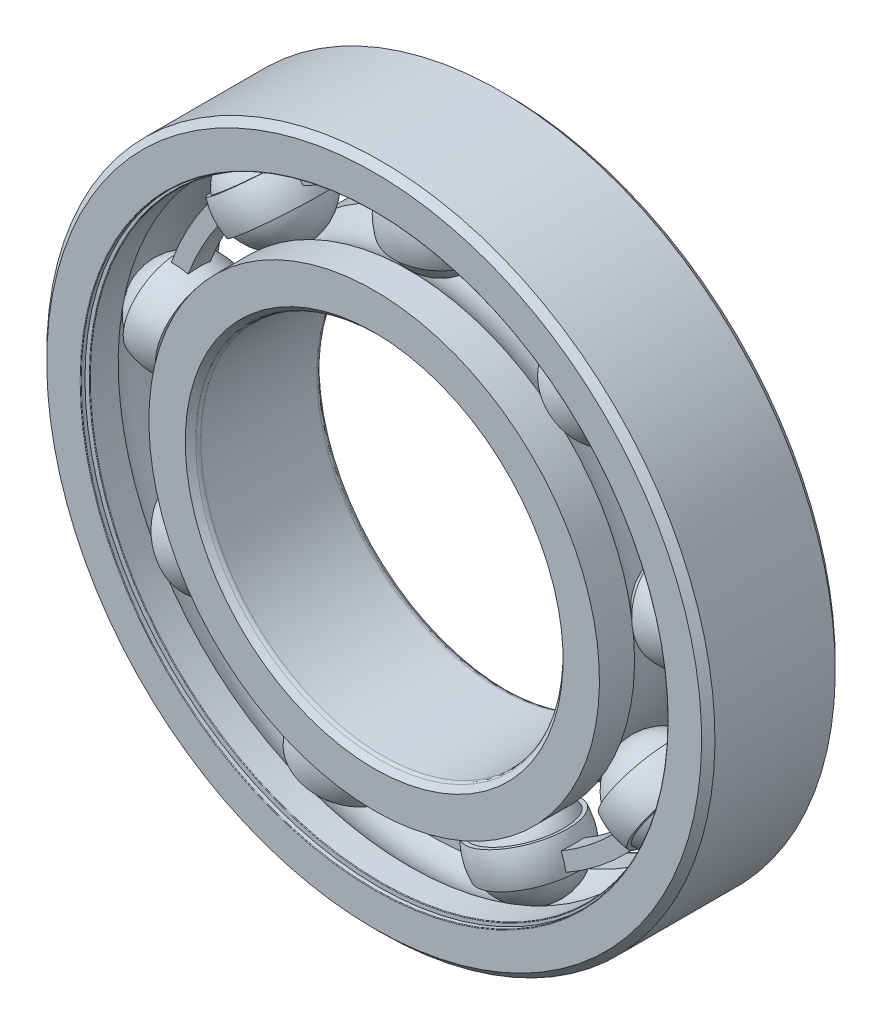
SolidWorks part; units mm, degrees
ref_plane "Front Plane" through (0, 0, 0) normal (0, 0, 1) x (1, 0, 0)
ref_plane "Top Plane" through (0, 0, 0) normal (0, 1, 0) x (1, 0, 0)
ref_plane "Right Plane" through (0, 0, 0) normal (1, 0, 0) x (0, 0, -1)
sketch "Sketch1" plane through (0, 0, 0) normal (0, 0, 1) x (1, 0, 0)
  line L0 (-55, 0) -> (55, 0) construction
  line L1 (-30, 0) -> (30, 0) construction
  circle A0 centre (0, 0) radius 30 construction
  circle A1 centre (0, 0) radius 55 construction
  point P3 (0, 0)
  point P6 (0, 0)
  point P7 (0, -30)
  point P11 (0, -55)
  point P12 (0, 30)
  point P13 (0, 55)
  dimension "OD" = 110
  dimension "ID" = 60
sketch "Sketch2" plane through (0, 0, 0) normal (1, 0, 0) x (0, 0, -1)
  line L0 (-11, 55) -> (11, 55) construction
  line L1 (0, 55) -> (0, -55) construction
  line L2 (9.9, 55) -> (-9.9, 55)
  line L3 (-9.9, 55) -> (-11, 53.9)
  line L4 (-11, 53.9) -> (-11, 47.9154)
  line L5 (-11, 47.9154) -> (-5.225, 47.9154)
  line L6 (11, 47.9154) -> (5.225, 47.9154)
  line L7 (11, 53.9) -> (11, 47.9154)
  line L8 (9.9, 55) -> (11, 53.9)
  line L9 (0, 55) -> (0, 42.5) construction
  line L10 (0, 42.5) -> (0, 30) construction
  line L11 (0, 55) -> (0, -55) construction
  line L12 (-11, 0) -> (11, 0) construction
  line L13 (11, 30) -> (-11, 30) construction
  line L14 (0, 50.0251) -> (0, 34.9749) construction
  line L15 (-11, -30) -> (11, -30) construction
  line L16 (-11, -30) -> (-11, 30) construction
  line L17 (11, 55) -> (11, -55) construction
  arc A0 (-5.225, 47.9154) -> (5.225, 47.9154) centre (0, 42.5) cw
  circle A1 centre (0, 42.5) radius 7.5251 construction
  point P14 (0, 30)
  point P17 (0, 0)
  point P21 (0, 55)
  point P29 (0, 30)
  point P30 (0, -30)
  point P35 (0, 50.0251)
  dimension "Approx. Ball Dia." = 15.0502
  dimension "Width" = 22
  dimension "D1" = 45
  dimension "D2" = 1.1
  dimension "D3" = 10.45
  dimension "D4" = 5.4154
  dimension "For Shaft Diameter" = 60
  dimension "For Housing ID" = 110
sketch "Sketch3" plane through (0, 0, 0) normal (1, 0, 0) x (0, 0, -1)
  line L0 (9.9, 55) -> (11, 53.9) construction
  line L1 (11, 53.9) -> (11, 47.9154) construction
  line L2 (11, 47.9154) -> (5.225, 47.9154) construction
  line L3 (-11, 47.9154) -> (-5.225, 47.9154) construction
  line L4 (-11, 53.9) -> (-11, 47.9154) construction
  line L5 (-9.9, 55) -> (-11, 53.9) construction
  line L6 (9.9, 55) -> (-9.9, 55) construction
  line L7 (9.9, 55) -> (11, 53.9)
  line L8 (11, 53.9) -> (11, 47.9154)
  line L9 (11, 47.9154) -> (5.225, 47.9154)
  line L10 (-11, 47.9154) -> (-5.225, 47.9154)
  line L11 (-11, 53.9) -> (-11, 47.9154)
  line L12 (-9.9, 55) -> (-11, 53.9)
  line L13 (9.9, 55) -> (-9.9, 55)
  arc A0 (5.225, 47.9154) -> (-5.225, 47.9154) centre (0, 42.5) ccw construction
  arc A1 (5.225, 47.9154) -> (-5.225, 47.9154) centre (0, 42.5) ccw
revolve "Revolve1" add sketch "Sketch3" angle 360 about L12
sketch "Sketch8" plane through (0, 0, 0) normal (1, 0, 0) x (0, 0, -1)
  line L0 (-11, 47.9154) -> (-5.225, 47.9154) construction
  line L1 (-10.296, 47.9154) -> (-9.9, 47.9154)
  line L2 (-10.296, 47.9154) -> (-10.296, 50.2769) construction
  line L3 (-10.296, 50.2769) -> (-9.9, 50.2769)
  line L4 (-9.9, 47.9154) -> (-9.9, 50.2769)
  line L5 (11, 47.9154) -> (5.225, 47.9154) construction
  line L6 (9.9, 47.9154) -> (10.296, 47.9154)
  line L7 (9.9, 47.9154) -> (9.9, 50.2769)
  line L8 (9.9, 50.2769) -> (10.296, 50.2769)
  line L9 (10.296, 47.9154) -> (10.296, 50.2769) construction
  line L10 (-9.9, 50.2769) -> (9.9, 50.2769) construction
  line L11 (0, 55) -> (0, -55) construction
  line L12 (-10.296, 50.2769) -> (-10.296, 52.6385) construction
  line L13 (-10.296, 52.6385) -> (-10.296, 55) construction
  line L14 (-11, 55) -> (11, 55) construction
  line L15 (-10.296, 47.9154) -> (-11, 47.9154)
  line L16 (-11, 47.9154) -> (-11, 48.3114)
  line L17 (-11, 53.9) -> (-11, 47.9154) construction
  line L18 (-11, 48.3114) -> (-10.296, 48.3114)
  line L19 (-10.296, 48.3114) -> (-10.296, 50.2769)
  line L20 (10.296, 47.9154) -> (11, 47.9154)
  line L21 (11, 47.9154) -> (11, 48.3114)
  line L22 (11, 53.9) -> (11, 47.9154) construction
  line L23 (11, 48.3114) -> (10.296, 48.3114)
  line L24 (10.296, 48.3114) -> (10.296, 50.2769)
  point P12 (0, 50.2769)
  dimension "D1" = 19.8
  dimension "D2" = 0.396
revolve "Cut-Revolve1" cut sketch "Sketch8" angle 360 about L12
sketch "Sketch4" plane through (0, 0, 0) normal (1, 0, 0) x (0, 0, -1)
  line L0 (0, 55) -> (0, -55) construction
  line L1 (0, 55) -> (0, -55) construction
  line L2 (-9.9, 30) -> (-11, 31.1)
  line L3 (-11, 31.1) -> (-11, 37.0846)
  line L5 (-11, 37.0846) -> (-5.225, 37.0846)
  line L6 (-9.9, 30) -> (9.9, 30)
  line L8 (9.9, 30) -> (11, 31.1)
  line L10 (11, 31.1) -> (11, 37.0846)
  line L11 (11, 37.0846) -> (5.225, 37.0846)
  line L12 (-11, 53.9) -> (-11, 47.9154) construction
  line L13 (9.9, 55) -> (11, 53.9) construction
  line L15 (11, -53.9) -> (11, 53.9) construction
  line L16 (9.9, 55) -> (9.9, -55) construction
  arc A1 (5.225, 37.0846) -> (-5.225, 37.0846) centre (0, 42.5) cw
  circle A2 centre (0, 42.5) radius 7.5251 construction
  point P1 (0, 30)
revolve "Revolve2" add sketch "Sketch4" angle 360 about L12
sketch "Sketch5" plane through (0, 0, 0) normal (1, 0, 0) x (0, 0, -1)
  line L0 (-7.5251, 42.5) -> (7.5251, 42.5)
  arc A2 (-7.5251, 42.5) -> (7.5251, 42.5) centre (0, 42.5) cw
  arc A3 (5.225, 47.9154) -> (-5.225, 47.9154) centre (0, 42.5) ccw construction
revolve "Revolve3" add sketch "Sketch5" angle 360 about L0
sketch "Sketch6" plane through (0, 0, 0) normal (1, 0, 0) x (0, 0, -1)
  line L0 (-5.225, 47.9154) -> (-5.225, 45.2077) construction
  line L1 (-5.225, 45.2077) -> (-5.225, 42.5) construction
  line L2 (-5.225, 42.5) -> (-5.225, 39.7923) construction
  line L3 (-5.225, 39.7923) -> (-5.225, 37.0846) construction
  line L4 (-11, 45.2077) -> (-10.3368, 45.2077) construction
  line L5 (-5.225, 45.2077) -> (-5.225, 39.7923) construction
  line L7 (-10.3368, 45.2077) -> (-9.6737, 45.2077) construction
  line L8 (-9.6737, 45.2077) -> (-9.0105, 45.2077) construction
  line L10 (0, 55) -> (0, -55) construction
  line L11 (0, 55) -> (0, -55) construction
  line L12 (-11, 47.9154) -> (-11, 45.2077) construction
  line L13 (-7.6842, 45.2077) -> (-7.0211, 45.2077) construction
  line L14 (-11, 53.9) -> (-11, -53.9) construction
  line L15 (-11, 45.2077) -> (-11, 42.5) construction
  line L16 (-11, 42.5) -> (-11, 39.7923) construction
  line L17 (-11, 39.7923) -> (-11, 37.0846) construction
  line L18 (-9.0105, 45.2077) -> (-8.3474, 45.2077) construction
  line L19 (-8.3474, 45.2077) -> (-7.6842, 45.2077) construction
  line L20 (-7.0211, 45.2077) -> (-7.6842, 45.2077)
  line L21 (-11, 39.7923) -> (-10.3368, 39.7923) construction
  line L22 (-10.3368, 39.7923) -> (-9.6737, 39.7923) construction
  line L23 (-9.6737, 39.7923) -> (-9.0105, 39.7923) construction
  line L24 (-9.0105, 39.7923) -> (-8.3474, 39.7923) construction
  line L25 (-8.3474, 39.7923) -> (-7.6842, 39.7923) construction
  line L26 (-7.6842, 39.7923) -> (-7.0211, 39.7923) construction
  line L27 (-7.0211, 39.7923) -> (-7.6842, 39.7923)
  line L28 (-8.3474, 45.2077) -> (-8.3474, 39.7923) construction
  line L30 (-8.0158, 45.2077) -> (-8.0158, 39.7923) construction
  circle A0 centre (0, 42.5) radius 7.5251 construction
  arc A2 (-7.6842, 39.7923) -> (-7.6842, 45.2077) centre (3.2056, 42.5) cw
  arc A3 (-7.0211, 45.2077) -> (-7.0211, 39.7923) centre (0, 42.5) ccw
revolve "Revolve4" add sketch "Sketch6" angle 360 about L11
sketch "Sketch7" plane through (0, 0, 0) normal (0, 0, 1) x (1, 0, 0)
  line L0 (-7.5251, 42.5) -> (7.5251, 42.5) construction
  line L1 (0, 34.9749) -> (0, 50.0251) construction
  line L2 (0, 0) -> (14.5359, 39.9369) construction
  line L8 (0, 55) -> (0, -55) construction
  line L9 (27.3185, 32.5569) -> (29.0589, 34.6311)
  line L10 (0, 55) -> (0, -55) construction
  line L11 (0, 45.2077) -> (0, 42.5)
  arc A1 (27.3185, 32.5569) -> (0, 42.5) centre (0, 0) ccw
  arc A2 (29.0589, 34.6311) -> (0, 45.2077) centre (0, 0) ccw
  dimension "D1" = 40
  dimension "D2" = 15.0502
extrude "Boss-Extrude1" add sketch "Sketch7" along normal mid plane 3.6667
pattern_circular "CirPattern1" count 9 over 360 about axis through (0, 0, 11) along (0, 0, -1) of bodies 104 134
pattern_circular "CirPattern2" count 9 over 360 about axis through (0, 0, 11) along (0, 0, -1) of "Revolve4", "Boss-Extrude1" reverse direction yes
fillet "Fillet1" radius 0.099 4 edges at (0, -47.9154, -9.9) (0, -48.3114, -11) (0, -47.9154, 9.9) (0, -48.3114, 11)
fillet "Fillet2" radius 0.825 2 edges at (0, -30, -9.9) (0, -30, 9.9)
ref_plane "Plane1" through (14.5359, 39.9369, 0) normal (0.342, 0.9397, 0) x (0.9397, -0.342, 0)
sketch "Sketch9" plane through (14.5359, 39.9369, 0) normal (0.342, 0.9397, 0) x (0.9397, -0.342, 0)
  line L0 (-7.4646, -1.8333) -> (-7.4646, -5.5)
  line L1 (-7.4646, -5.5) -> (-3.2379, -5.5)
  line L2 (-3.2379, -5.5) -> (0, -2.7831)
  line L3 (0, -2.7831) -> (3.2379, -5.5)
  line L4 (3.2379, -5.5) -> (7.4646, -5.5)
  line L5 (7.4646, -5.5) -> (7.4646, -1.8333)
  line L6 (7.4646, -1.8333) -> (-7.4646, -1.8333)
  line L7 (0, -1.8333) -> (0, 0) construction
  line L8 (-7.4646, -1.8333) -> (-7.4646, 0) construction
  dimension "D1" = 3.6667
  dimension "D2" = 1.8333
  dimension "D3" = 40
extrude "Boss-Extrude2" [suppressed] add sketch "Sketch9" along normal blind 6.5845 draft 15 and the other way blind 6.5845 draft 10 separate body draft outward yes other way draft outward yes
fillet "Fillet3" [suppressed] radius 1.1
mirror "Mirror1" [suppressed] about plane through (0, 0, 0) normal (0, 0, 1) of bodies 149
pattern_circular "CirPattern3" [suppressed] count 9 over 360 about axis through (0, 0, 11) along (0, 0, -1) of bodies 158 149
equation "\"D2@Sketch2\" = \"Width@Sketch2\" * .05"
equation "\"D3@Sketch2\"=\"Width@Sketch2\" * .475"
equation "\"D4@Sketch2\" =  (  (  ( \"OD@Sketch1\" - \"Width@Sketch2\" )  / 2 )  / 3.25 )  / 2.5"
equation "\"D1@Boss-Extrude1\" = \"Width@Sketch2\" / 6"
equation "\"D1@Sketch8\"=\"Width@Sketch2\"*.9"
equation "\"D2@Sketch8\"=\"D1@Sketch8\"*.02"
equation "\"D1@Fillet1\" = \"D2@Sketch8\" * .25"
equation "\"D1@Fillet2\" = \"D2@Sketch2\" * .75"
equation "\"Approx No of Balls@CirPattern1\" = ( pi * \"OD@Sketch1\" ) * .4 / \"Approx. Ball Dia.@Sketch2\""
equation "\"D1@Sketch7\" = 360 / \"Approx No of Balls@CirPattern1\""
equation "\"D1@CirPattern2\" = \"Approx No of Balls@CirPattern1\""
equation "\"D2@Sketch7\"=\"Approx. Ball Dia.@Sketch2\""
equation "\"D2@Sketch9\" = \"D1@Boss-Extrude1\" * .5"
equation "\"D1@Sketch9\"=\"D2@Sketch9\"*2"
equation "\"D1@Boss-Extrude2\"=\"Approx. Ball Dia.@Sketch2\"*.4375"
equation "\"D2@Boss-Extrude2\"=\"D1@Boss-Extrude2\""
equation "\"D1@CirPattern3\" = \"Approx No of Balls@CirPattern1\""
equation "\"D1@Fillet3\"=\"D1@Sketch9\" * .3"
